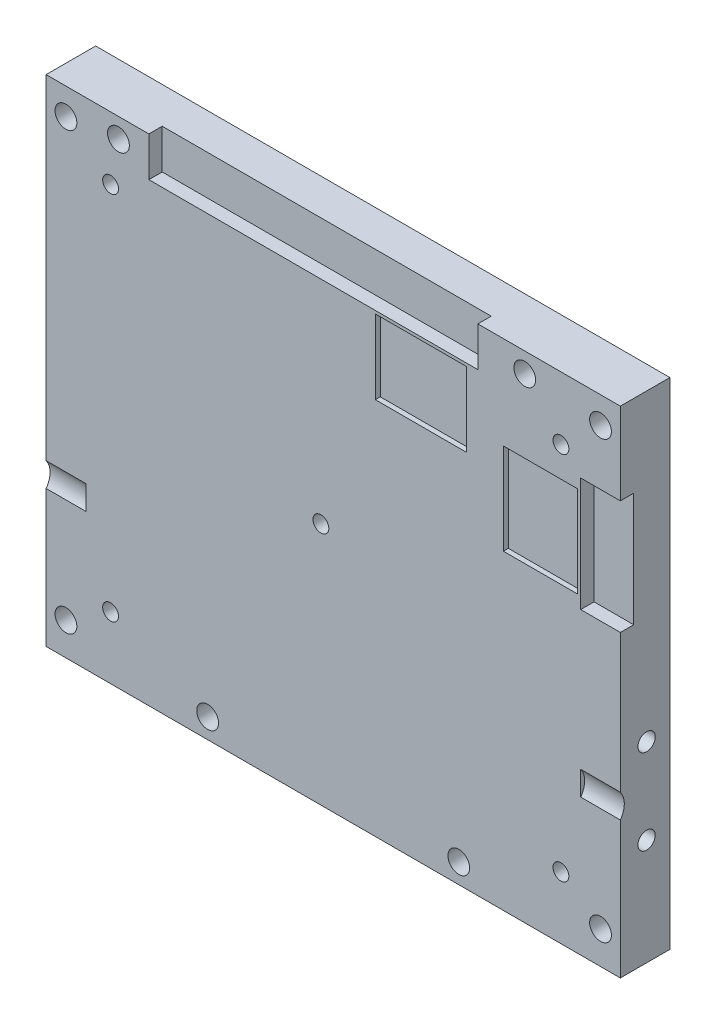
SolidWorks part; units mm, degrees
material "6061-T6 (SS)"
ref_plane "前视基准面" through (0, 0, 0) normal (0, 0, 1) x (1, 0, 0)
ref_plane "上视基准面" through (0, 0, 0) normal (0, 1, 0) x (1, 0, 0)
ref_plane "右视基准面" through (0, 0, 0) normal (1, 0, 0) x (0, 0, -1)
other "Configuration Table"
sketch "草图1" plane through (0, 0, 0) normal (0, 0, 1) x (1, 0, 0)
  line L1 (-4.3, -4.3) -> (53.65, -4.3)
  line L2 (-4.3, -4.3) -> (-4.3, 45.68)
  line L3 (-4.3, 45.68) -> (53.65, 45.68)
  line L4 (53.65, -4.3) -> (53.65, 45.68)
  dimension "D1" = 53.65
  dimension "D2" = 4.3
  dimension "D3" = 45.68
  dimension "D4" = 4.3
extrude "Flat_Base_5mm" add sketch "草图1" along normal blind 5
move or copy body "Stock_Z_Position" bodies to move or copy 106 copy no translate (0, 0, -2.7519) parameters "D1"=0, "D2"=0, "D3"=2.7519
sketch "草图2" plane through (0, 0, 2.2481) normal (0, 0, 1) x (1, 0, 0)
  circle A0 centre (-2.3, -1) radius 1.1
  circle A1 centre (-2.3, 43) radius 1.1
  circle A2 centre (51.65, -1) radius 1.1
  circle A3 centre (51.65, 43) radius 1.1
  circle A4 centre (12, -2.3) radius 1.1
  circle A5 centre (37.35, -2.3) radius 1.1
  circle A6 centre (3, 43.68) radius 1.1
  circle A7 centre (44, 43.68) radius 1.1
  dimension "D1" = 2.2
  dimension "D2" = 3
  dimension "D3" = 12
  dimension "D4" = 37.35
  dimension "D5" = 44
  dimension "D6" = 51.65
  dimension "D7" = 2.3
  dimension "D8" = 43
  dimension "D9" = 43.68
  dimension "D10" = 1
  dimension "D11" = 2.3
extrude "Frame_8xD2p2_Through" cut sketch "草图2" against normal through all
sketch "草图3" plane through (0, 0, 2.2481) normal (0, 0, 1) x (1, 0, 0)
  circle A0 centre (23.4283, 20.2768) radius 0.8
  circle A1 centre (2.2063, 39.3338) radius 0.8
  circle A2 centre (47.6533, 39.3338) radius 0.8
  circle A3 centre (47.6533, 1.9767) radius 0.8
  circle A4 centre (2.2063, 1.9767) radius 0.8
  dimension "D1" = 1.6
  dimension "D2" = 2.2063
  dimension "D3" = 23.4283
  dimension "D4" = 47.6533
  dimension "D5" = 1.9767
  dimension "D6" = 20.2768
  dimension "D7" = 39.3338
extrude "PCB_5xD1p6_M2_Through" cut sketch "草图3" against normal through all
cosmetic thread "PCB_M2_Cosmetic_1" parameters "D2"=2
cosmetic thread "PCB_M2_Cosmetic_2" parameters "D2"=2
cosmetic thread "PCB_M2_Cosmetic_3" parameters "D2"=2
cosmetic thread "PCB_M2_Cosmetic_4" parameters "D2"=2
cosmetic thread "PCB_M2_Cosmetic_5" parameters "D2"=2
sketch "草图4" plane through (-4.3, 0, 0) normal (-1, 0, 0) x (0, 0, 1)
  circle A0 centre (3.8995, 10.725) radius 2.05
  dimension "D1" = 4.1
  dimension "D2" = 3.8995
  dimension "D3" = 10.725
extrude "SMA_Center_Matching_Arc" cut sketch "草图4" against normal blind 4
sketch "草图5" plane through (-4.3, 0, 0) normal (-1, 0, 0) x (0, 0, 1)
  circle A0 centre (-0.4005, 6.425) radius 0.875
  circle A1 centre (-0.4005, 15.025) radius 0.875
  dimension "D1" = 1.75
  dimension "D2" = 0.4005
  dimension "D3" = 6.425
  dimension "D4" = 15.025
extrude "SMA_Lower_2xD1p75_Blind4" cut sketch "草图5" against normal blind 4
cosmetic thread "SMA_Lower_Cosmetic_1" parameters "D1"=3.5, "D2"=2.2
cosmetic thread "SMA_Lower_Cosmetic_2" parameters "D1"=3.5, "D2"=2.2
sketch "草图6" plane through (53.65, 0, 0) normal (1, 0, 0) x (0, 0, -1)
  circle A0 centre (-3.8995, 10.725) radius 2.05
  dimension "D1" = 4.1
  dimension "D2" = 3.8995
  dimension "D3" = 10.725
extrude "切除-拉伸5" cut sketch "草图6" against normal blind 4
sketch "草图7" plane through (53.65, 0, 0) normal (1, 0, 0) x (0, 0, -1)
  circle A0 centre (0.4005, 6.425) radius 0.875
  circle A1 centre (0.4005, 15.025) radius 0.875
  dimension "D1" = 1.75
  dimension "D2" = 0.4005
  dimension "D3" = 6.425
  dimension "D4" = 15.025
extrude "切除-拉伸6" cut sketch "草图7" against normal blind 4
cosmetic thread "装饰螺纹线8" parameters "D1"=3.5, "D2"=2.2
cosmetic thread "装饰螺纹线9" parameters "D1"=3.5, "D2"=2.2
sketch "草图8" plane through (53.65, 0, 0) normal (1, 0, 0) x (0, 0, -1)
  line L1 (-0.9, 25.9) -> (-7.6, 25.9)
  line L2 (-0.9, 25.9) -> (-0.9, 37.4)
  line L3 (-0.9, 37.4) -> (-7.6, 37.4)
  line L4 (-7.6, 25.9) -> (-7.6, 37.4)
  dimension "D1" = 0.9
  dimension "D2" = 7.6
  dimension "D3" = 25.9
  dimension "D4" = 37.4
extrude "Right_TypeC_Window_Lower" cut sketch "草图8" against normal blind 4
sketch "草图9" plane through (0, 45.68, 0) normal (0, 1, 0) x (1, 0, 0)
  line L1 (6.07, -0.9) -> (39.273, -0.9)
  line L2 (6.07, -0.9) -> (6.07, -7.6)
  line L3 (6.07, -7.6) -> (39.273, -7.6)
  line L4 (39.273, -0.9) -> (39.273, -7.6)
  dimension "D1" = 6.07
  dimension "D2" = 39.273
  dimension "D3" = 0.9
  dimension "D4" = 7.6
extrude "Rear_Window_Lower" cut sketch "草图9" against normal blind 4
sketch "草图10" plane through (0, 0, 2.2481) normal (0, 0, 1) x (1, 0, 0)
  line L1 (41.85, 27.1) -> (49.35, 27.1)
  line L2 (41.85, 27.1) -> (41.85, 36.3)
  line L3 (41.85, 36.3) -> (49.35, 36.3)
  line L4 (49.35, 27.1) -> (49.35, 36.3)
  dimension "D1" = 41.85
  dimension "D2" = 49.35
  dimension "D3" = 27.1
  dimension "D4" = 36.3
extrude "TypeC_Bottom_Recess_A" cut sketch "草图10" against normal blind 0.5
sketch "草图11" plane through (0, 0, 2.2481) normal (0, 0, 1) x (1, 0, 0)
  line L1 (28.923, 33.88) -> (38.123, 33.88)
  line L2 (28.923, 33.88) -> (28.923, 41.38)
  line L3 (28.923, 41.38) -> (38.123, 41.38)
  line L4 (38.123, 33.88) -> (38.123, 41.38)
  dimension "D1" = 28.923
  dimension "D2" = 38.123
  dimension "D3" = 33.88
  dimension "D4" = 41.38
extrude "TypeC_Bottom_Recess_B" cut sketch "草图11" against normal blind 0.5
